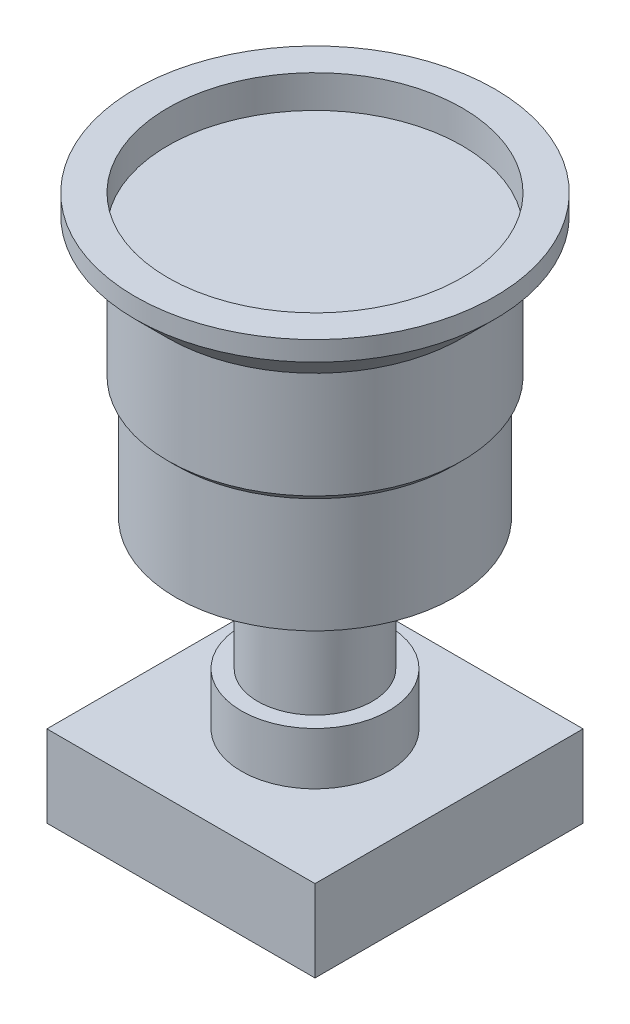
SolidWorks part; units mm, degrees
ref_plane "Front Plane" through (0, 0, 0) normal (0, 0, 1) x (1, 0, 0)
ref_plane "Top Plane" through (0, 0, 0) normal (0, 1, 0) x (1, 0, 0)
ref_plane "Right Plane" through (0, 0, 0) normal (1, 0, 0) x (0, 0, -1)
sketch "Sketch1" plane through (0, 0, 0) normal (0, 1, 0) x (1, 0, 0)
  line L1 (0, 0) -> (164, 0)
  line L2 (0, 0) -> (0, 164)
  line L3 (0, 164) -> (164, 164)
  line L4 (164, 0) -> (164, 164)
  dimension "D1" = 164
  dimension "D2" = 164
extrude "Boss-Extrude1" add sketch "Sketch1" along normal blind 50
sketch "Sketch2" plane through (0, 50, 0) normal (0, 1, 0) x (1, 0, 0)
  line L0 (82, 164) -> (82, 0) construction
  line L1 (164, 164) -> (0, 164) construction
  line L2 (0, 0) -> (164, 0) construction
  line L3 (0, 82) -> (164, 82) construction
  line L4 (0, 164) -> (0, 0) construction
  line L5 (164, 0) -> (164, 164) construction
  circle A0 centre (82, 82) radius 45
  dimension "D1" = 90
extrude "Boss-Extrude2" add sketch "Sketch2" along normal blind 32
sketch "Sketch3" plane through (0, 82, 0) normal (0, 1, 0) x (1, 0, 0)
  circle A0 centre (82, 82) radius 35
  dimension "D1" = 70
extrude "Boss-Extrude3" add sketch "Sketch3" along normal blind 45
sketch "Sketch4" plane through (0, 127, 0) normal (0, 1, 0) x (1, 0, 0)
  circle A0 centre (82, 82) radius 42.5
  dimension "D1" = 85
extrude "Boss-Extrude4" add sketch "Sketch4" along normal blind 25
sketch "Sketch5" plane through (0, 152, 0) normal (0, 1, 0) x (1, 0, 0)
  circle A0 centre (82, 82) radius 85
  dimension "D1" = 170
extrude "Boss-Extrude5" add sketch "Sketch5" along normal blind 80
sketch "Sketch6" plane through (0, 232, 0) normal (0, 1, 0) x (1, 0, 0)
  circle A0 centre (82, 82) radius 90
  dimension "D1" = 180
extrude "Boss-Extrude6" add sketch "Sketch6" along normal blind 70
sketch "Sketch7" plane through (0, 302, 0) normal (0, 1, 0) x (1, 0, 0)
  circle A0 centre (82, 82) radius 110
  dimension "D1" = 220
extrude "Boss-Extrude7" add sketch "Sketch7" along normal blind 32
chamfer "Chamfer1" distance 20 angle 45 1 edges at (82, 302, 28)
chamfer "Chamfer2" distance 5 angle 45 1 edges at (82, 232, 8)
chamfer "Chamfer3" distance 10 angle 80 1 edges at (82, 152, 3) first distance on face at (82, 232, 3)
chamfer "Chamfer4" distance 5 angle 60 1 edges at (82, 127, -39.5) first distance on face at (82, 154.5061, -39.5)
sketch "Sketch8" plane through (0, 334, 0) normal (0, 1, 0) x (1, 0, 0)
  circle A0 centre (82, 82) radius 90
  circle A1 centre (82, 82) radius 110 construction
  dimension "D1" = 20
extrude "Cut-Extrude1" cut sketch "Sketch8" against normal blind 20
